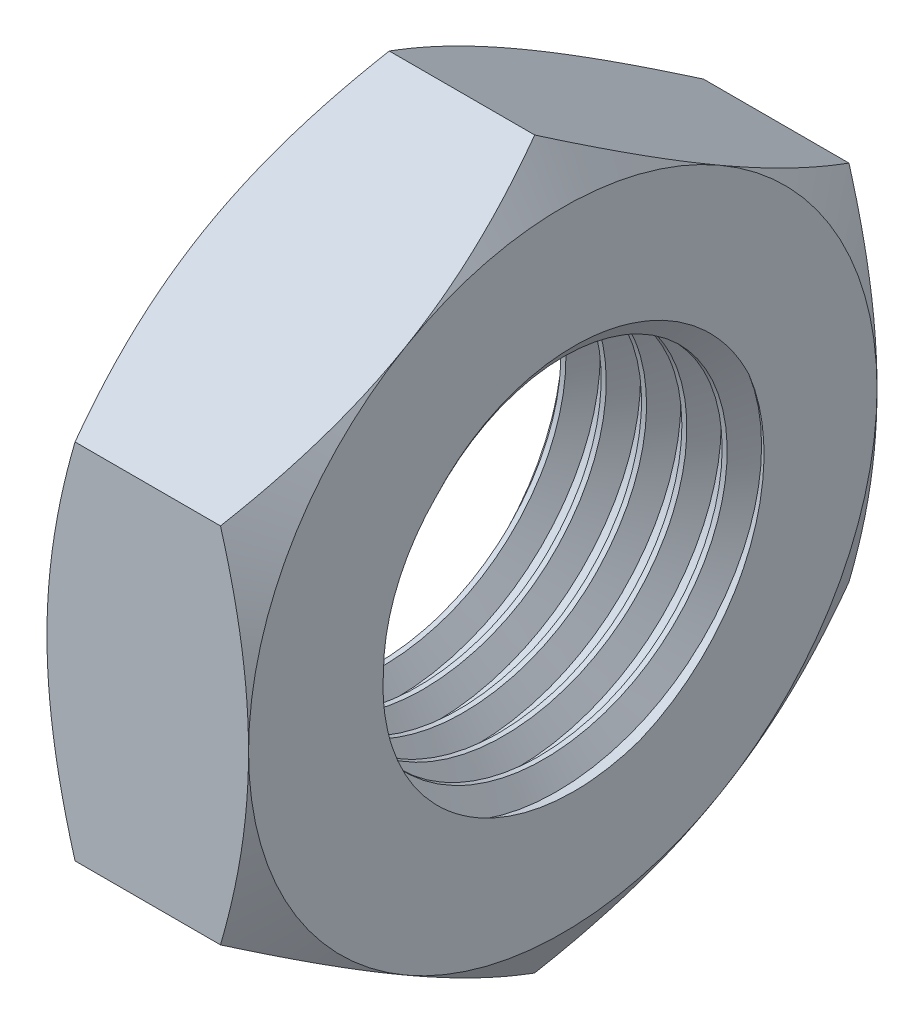
SolidWorks part; units mm, degrees
ref_plane "Front Plane" through (0, 0, 0) normal (0, 0, 1) x (1, 0, 0)
ref_plane "Top Plane" through (0, 0, 0) normal (0, 1, 0) x (1, 0, 0)
ref_plane "Right Plane" through (0, 0, 0) normal (1, 0, 0) x (0, 0, -1)
sketch "Sketch1" plane through (0, 0, 0) normal (0, 0, 1) x (1, 0, 0)
  line L0 (0, 0) -> (-5, 0) construction
  line L1 (0, 4.45) -> (0, 7.7942)
  line L2 (-7.7942, -4.5) -> (0, -9) construction
  line L3 (0, -9) -> (7.7942, -4.5) construction
  line L4 (7.7942, -4.5) -> (7.7942, 4.5) construction
  line L5 (7.7942, 4.5) -> (0, 9) construction
  line L6 (0, 9) -> (-7.7942, 4.5) construction
  line L7 (-7.7942, 4.5) -> (-7.7942, -4.5) construction
  line L8 (0, 7.7942) -> (-0.6962, 9)
  line L9 (-0.6962, 9) -> (-4.3038, 9)
  line L10 (-4.3038, 9) -> (-5, 7.7942)
  line L13 (-5, 7.7942) -> (-5, 4.45)
  line L14 (-5, 4.45) -> (0, 4.45)
  circle A0 centre (0, 0) radius 7.7942 construction
  point P12 (0, 0)
  dimension "D1" = 5
  dimension "D2" = 9
  dimension "D3" = 30
  dimension "D4" = 30
  dimension "D5" = 4.45
revolve "Revolve1" add sketch "Sketch1" angle 360 about L0
sketch "Sketch2" plane through (0, 0, 0) normal (1, 0, 0) x (0, 0, -1)
  line L1 (0, 9) -> (-7.7942, 4.5)
  line L2 (-7.7942, 4.5) -> (-7.7942, -4.5)
  line L3 (-7.7942, -4.5) -> (0, -9)
  line L4 (0, -9) -> (7.7942, -4.5)
  line L5 (7.7942, -4.5) -> (7.7942, 4.5)
  line L6 (7.7942, 4.5) -> (0, 9)
  circle A0 centre (0, 0) radius 7.7942 construction
  circle A1 centre (0, 0) radius 9 construction
  point P1 (0, 0)
extrude "Cut-Extrude1" cut sketch "Sketch2" against normal through all flip side to cut
thread "Thread1" pitch 1 method cut profile "Thread Profile1" start angle 0, offset 1, length 0, pitch 1, diameter 8.9
ref_plane "Plane1" through (1, 0, 4.45) normal (0, 1, 0) x (0, 0, -1)
sketch "Thread Profile1" plane through (1, 0, 4.45) normal (0, 1, 0) x (0, 0, -1)
  line L0 (0, 0) -> (0, 1) construction
  line L11 (0, 0) -> (0, 0.875)
  line L12 (0, 0.875) -> (-0.5413, 0.5625)
  line L13 (-0.5413, 0.5625) -> (-0.5413, 0.3125)
  line L15 (-0.5413, 0.3125) -> (0, 0)
  line L17 (-0.5413, 0.4375) -> (0, 0.4375) construction
  point P2 (0, 0)
  dimension "Pitch" = 1
  dimension "Profile_Angle" = 60
  dimension "Profile_Land" = 0.25
  dimension "Profile_Height" = 0.5413
